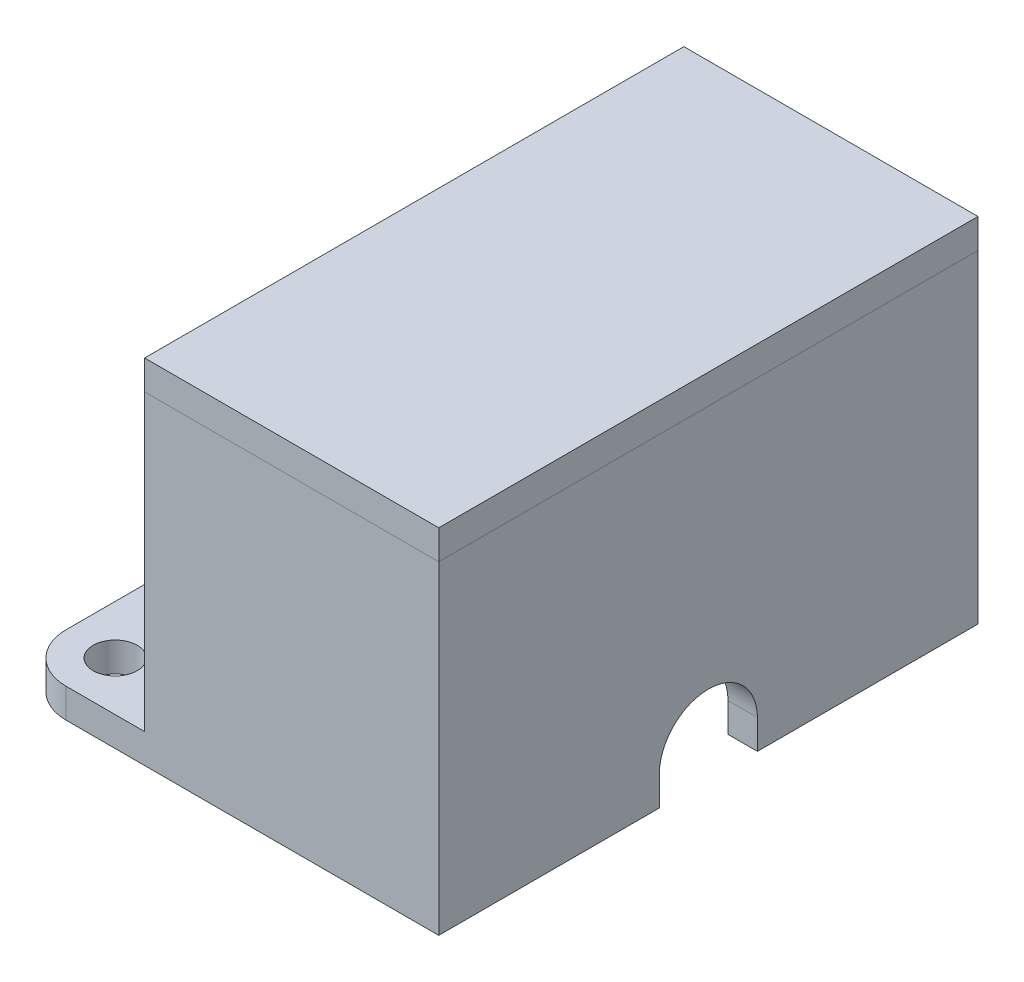
SolidWorks part; units mm, degrees
ref_plane "Front Plane" through (0, 0, 0) normal (0, 0, 1) x (1, 0, 0)
ref_plane "Top Plane" through (0, 0, 0) normal (0, 1, 0) x (1, 0, 0)
ref_plane "Right Plane" through (0, 0, 0) normal (1, 0, 0) x (0, 0, -1)
sketch "Sketch1" plane through (0, 0, 0) normal (0, 1, 0) x (1, 0, 0)
  line L1 (-15, -27.5) -> (15, -27.5)
  line L2 (-15, -27.5) -> (-15, 27.5)
  line L3 (-15, 27.5) -> (15, 27.5)
  line L4 (15, -27.5) -> (15, 27.5)
  line L5 (-15, -27.5) -> (15, 27.5) construction
  line L6 (-15, 27.5) -> (15, -27.5) construction
  point P0 (0, 0)
  dimension "D1" = 55
  dimension "D2" = 30
extrude "Boss-Extrude7" add sketch "Sketch1" against normal blind 3
sketch "Sketch14" plane through (0, -3, 0) normal (0, -1, 0) x (1, 0, 0)
  line L0 (12, -24.5) -> (12, 24.5)
  line L1 (12, 24.5) -> (-12, 24.5)
  line L2 (-12, 24.5) -> (-12, -24.5)
  line L3 (-12, -24.5) -> (12, -24.5)
  line L4 (15, -27.5) -> (15, 27.5)
  line L5 (15, 27.5) -> (-15, 27.5)
  line L6 (-15, 27.5) -> (-15, -27.5)
  line L7 (-15, -27.5) -> (15, -27.5)
  line L8 (15, -27.5) -> (15, 27.5)
  line L9 (15, 27.5) -> (-15, 27.5)
  line L10 (-15, 27.5) -> (-15, -27.5)
  line L11 (-15, -27.5) -> (15, -27.5)
  dimension "D1" = 0
  dimension "D2" = 3
extrude "Boss-Extrude8" add sketch "Sketch14" along normal blind 33 separate body
sketch "Sketch17" plane through (15, 0, 0) normal (1, 0, 0) x (0, 0, -1)
  line L0 (-5, -36) -> (-5, -33)
  line L1 (27.5, -36) -> (-27.5, -36) construction
  line L2 (5, -33) -> (5, -36)
  line L3 (5, -36) -> (-5, -36)
  arc A0 (-5, -33) -> (5, -33) centre (0, -33) cw
  point P6 (0, -36)
  dimension "D1" = 10
  dimension "D2" = 3
extrude "Cut-Extrude1" cut sketch "Sketch17" against normal up to surface (3 mm away) up to face at (12, -19.5, 0)
sketch "Sketch23" plane through (0, -36, 0) normal (0, -1, 0) x (1, 0, 0)
  line L2 (-23, 7.5) -> (-15, 7.5) construction
  line L3 (-23, 22.5) -> (-23, 27.5) construction
  line L4 (15, 27.5) -> (-15, 27.5) construction
  line L5 (-15, 27.5) -> (-15, -27.5) construction
  line L7 (189.8967, 22.5) -> (189.8967, -7.5) construction
  line L8 (-23, -7.5) -> (-23, 22.5)
  dimension "D1" = 8
  dimension "D2" = 5
sketch "Sketch24" plane through (0, -36, 0) normal (0, -1, 0) x (1, 0, 0)
  line L0 (-15, 27.5) -> (-23, 27.5)
  line L1 (-15, 27.5) -> (-15, -27.5) construction
  line L2 (-28, 22.5) -> (-28, -7.5)
  line L3 (-23, -12.5) -> (-15, -12.5)
  line L4 (-15, -12.5) -> (-15, 27.5)
  line L5 (15, 27.5) -> (-15, 27.5) construction
  arc A0 (-23, 27.5) -> (-28, 22.5) centre (-23, 22.5) ccw
  arc A1 (-28, -7.5) -> (-23, -12.5) centre (-23, -7.5) ccw
  point P9 (-15, 31.7888)
extrude "Boss-Extrude11" add sketch "Sketch24" against normal blind 3
hole_wizard "#8 Clearance Hole2" positions "Sketch25" profile "Sketch26" hole size "#8" standard "ANSI Inch" end condition through all
sketch "Sketch25" plane through (0, -33, 0) normal (0, 1, 0) x (1, 0, 0)
  point P0 (-23, 7.5)
  point P3 (-23, -22.5)
sketch "Sketch26" plane through (-23, -33, -7.5) normal (1, 0, 0) x (0, 0, 1)
  line L0 (0, 0) -> (0, 3)
  line L1 (0, 3) -> (2.2479, 3)
  line L2 (2.2479, 3) -> (2.2479, 0)
  line L5 (2.2479, 0) -> (0, 0)
  line L11 (0, -6.35) -> (0, 107.95) construction
  dimension "Thru Hole Dia." = 4.4958
  dimension "Thru Hole Depth" = 3
